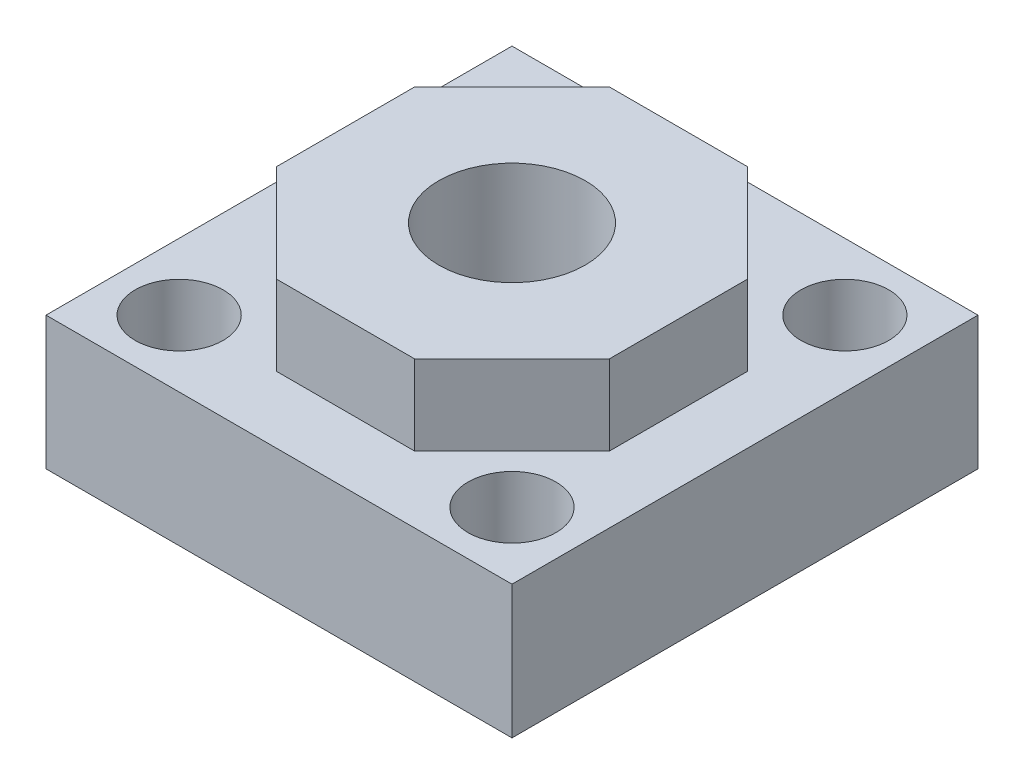
SolidWorks part; units mm, degrees
ref_plane "Front Plane" through (0, 0, 0) normal (0, 0, 1) x (1, 0, 0)
ref_plane "Top Plane" through (0, 0, 0) normal (0, 1, 0) x (1, 0, 0)
ref_plane "Right Plane" through (0, 0, 0) normal (1, 0, 0) x (0, 0, -1)
sketch "Sketch1" plane through (0, 0, 0) normal (0, 1, 0) x (1, 0, 0)
  line L1 (-17.5, 17.5) -> (17.5, 17.5)
  line L2 (-17.5, 17.5) -> (-17.5, -17.5)
  line L3 (-17.5, -17.5) -> (17.5, -17.5)
  line L4 (17.5, 17.5) -> (17.5, -17.5)
  line L5 (0, -17.5) -> (0, 17.5) construction
  line L6 (-17.5, 0) -> (17.5, 0) construction
  line L7 (5.1777, -12.5) -> (12.5, -5.1777)
  line L8 (12.5, -5.1777) -> (12.5, 5.1777)
  line L9 (12.5, 5.1777) -> (5.1777, 12.5)
  line L10 (5.1777, 12.5) -> (-5.1777, 12.5)
  line L11 (-5.1777, 12.5) -> (-12.5, 5.1777)
  line L12 (-12.5, 5.1777) -> (-12.5, -5.1777)
  line L13 (-12.5, -5.1777) -> (-5.1777, -12.5)
  line L14 (-5.1777, -12.5) -> (5.1777, -12.5)
  circle A0 centre (0, 0) radius 12.5 construction
  point P0 (0, 0)
  point P5 (12.5, 0)
  dimension "D1" = 35
  dimension "D2" = 35
  dimension "D3" = 25
extrude "Boss-Extrude1" add sketch "Sketch1" against normal blind 10 contours L13 L14 L7 L8 L9 L10 L11 L12 | L4 L1 L2 L3 L14 L13 L12 L11 L10 L9 L8 L7 region at (0, 0, -17.005) region at (0, 0, 0)
extrude "Boss-Extrude2" add sketch "Sketch1<3>" along normal blind 6 contours L13 L14 L7 L8 L9 L10 L11 L12 region at (0, 0, 0)
sketch "Sketch1<3>" plane through (0, 0, 0) normal (0, 1, 0) x (1, 0, 0) same geometry as "Sketch1"
hole_wizard "M10 Clearance Hole1" positions "Sketch2" profile "Sketch3" hole size "M10" standard "ISO" end condition through all
sketch "Sketch2" plane through (0, 6, 0) normal (0, 1, 0) x (1, 0, 0)
  point P0 (0, 0)
sketch "Sketch3" plane through (0, 6, 0) normal (1, 0, 0) x (0, 0, 1)
  line L0 (0, 0) -> (0, 16)
  line L1 (0, 16) -> (5.5, 16)
  line L2 (5.5, 16) -> (5.5, 0)
  line L5 (5.5, 0) -> (0, 0)
  line L11 (0, -6.35) -> (0, 107.95) construction
  dimension "Thru Hole Dia." = 11
  dimension "Thru Hole Depth" = 16
hole_wizard "M6 Clearance Hole1" positions "Sketch4" profile "Sketch5" hole size "M6" standard "ISO" end condition through all
sketch "Sketch4" plane through (0, 0, 0) normal (0, 1, 0) x (1, 0, 0)
  line L0 (-17.5, 17.5) -> (-17.5, -17.5) construction
  line L1 (-17.5, 17.5) -> (17.5, 17.5) construction
  point P0 (-12.5, 12.5)
  dimension "D1" = 5
  dimension "D2" = 5
sketch "Sketch5" plane through (-12.5, 0, -12.5) normal (1, 0, 0) x (0, 0, 1)
  line L0 (0, 0) -> (0, 10)
  line L1 (0, 10) -> (3.3, 10)
  line L2 (3.3, 10) -> (3.3, 0)
  line L5 (3.3, 0) -> (0, 0)
  line L11 (0, -6.35) -> (0, 107.95) construction
  dimension "Thru Hole Dia." = 6.6
  dimension "Thru Hole Depth" = 10
mirror "Mirror1" about plane through (0, 0, 0) normal (1, 0, 0) of "M6 Clearance Hole1"
mirror "Mirror2" about plane through (0, 0, 0) normal (0, 0, 1) of "Mirror1"
